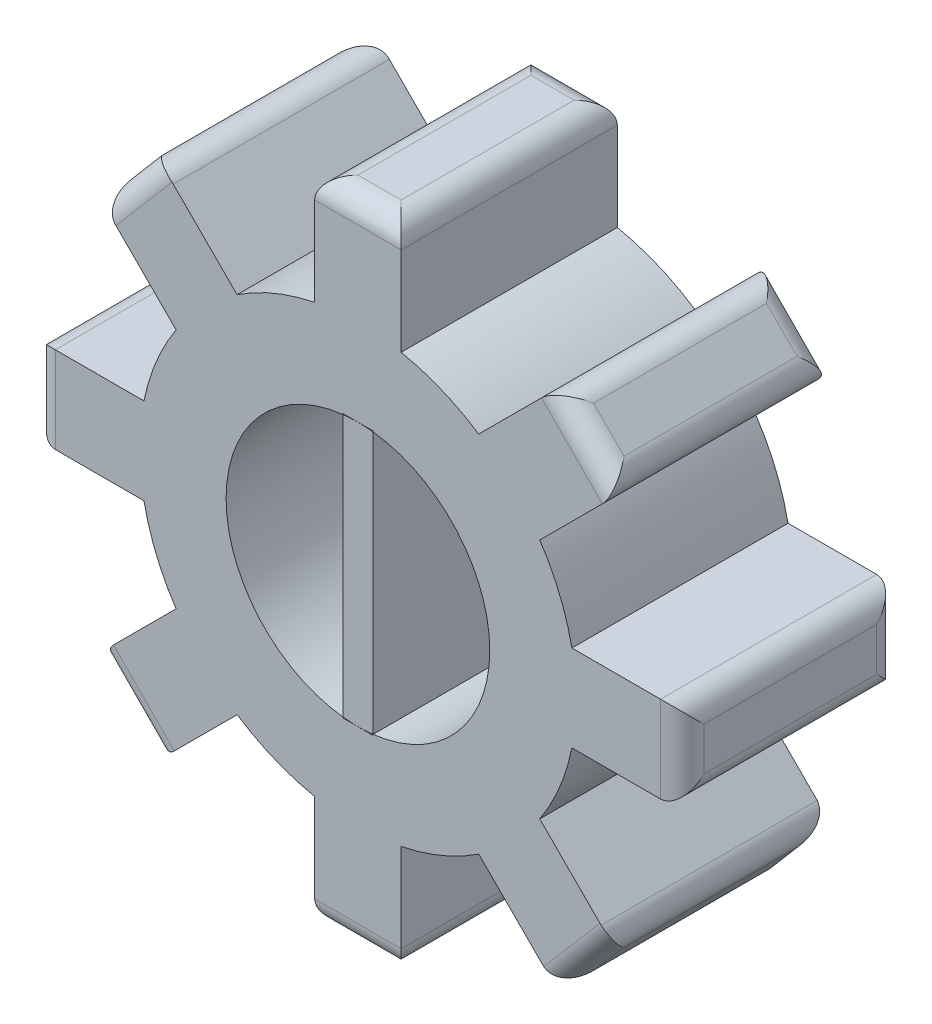
SolidWorks part; units mm, degrees
ref_plane "Front Plane" through (0, 0, 0) normal (0, 0, 1) x (1, 0, 0)
ref_plane "Top Plane" through (0, 0, 0) normal (0, 1, 0) x (1, 0, 0)
ref_plane "Right Plane" through (0, 0, 0) normal (1, 0, 0) x (0, 0, -1)
sketch "Sketch1" plane through (0, 0, 0) normal (0, 0, 1) x (1, 0, 0)
  line L1 (1, -7.5) -> (-1, -7.5)
  line L2 (1, -7.5) -> (1, 7.5)
  line L3 (1, 7.5) -> (-1, 7.5)
  line L4 (-1, -7.5) -> (-1, 7.5)
  line L5 (1, -7.5) -> (-1, 7.5) construction
  line L6 (1, 7.5) -> (-1, -7.5) construction
  line L7 (-7.5, -1) -> (7.5, -1)
  line L8 (-7.5, -1) -> (-7.5, 1)
  line L9 (-7.5, 1) -> (7.5, 1)
  line L10 (7.5, -1) -> (7.5, 1)
  line L11 (-7.5, -1) -> (7.5, 1) construction
  line L12 (-7.5, 1) -> (7.5, -1) construction
  line L13 (-6.007, -4.5928) -> (-4.5996, -6.0138)
  line L14 (-6.007, -4.5928) -> (4.5996, 6.0138)
  line L15 (4.5996, 6.0138) -> (6.007, 4.5928)
  line L16 (-4.5996, -6.0138) -> (6.007, 4.5928)
  line L17 (-6.007, -4.5928) -> (6.007, 4.5928) construction
  line L18 (4.5996, 6.0138) -> (-4.5996, -6.0138) construction
  line L22 (4.6549, -6.0646) -> (5.9517, -4.542)
  line L23 (4.6549, -6.0646) -> (-5.9517, 4.542)
  line L24 (-5.9517, 4.542) -> (-4.6549, 6.0646)
  line L25 (5.9517, -4.542) -> (-4.6549, 6.0646)
  line L26 (4.6549, -6.0646) -> (-4.6549, 6.0646) construction
  line L27 (-5.9517, 4.542) -> (5.9517, -4.542) construction
  line L29 (0.35, -3.05) -> (-0.35, -3.05)
  line L30 (0.35, -3.05) -> (0.35, 3.05)
  line L31 (0.35, 3.05) -> (-0.35, 3.05)
  line L32 (-0.35, -3.05) -> (-0.35, 3.05)
  line L33 (0.35, -3.05) -> (-0.35, 3.05) construction
  line L34 (0.35, 3.05) -> (-0.35, -3.05) construction
  circle A0 centre (0, 0) radius 3.05
  circle A1 centre (0, 0) radius 5.05
  point P20 (0, 0)
  dimension "D1" = 6.1
  dimension "D2" = 2
  dimension "D3" = 45
  dimension "D4" = 2
  dimension "D5" = 135
  dimension "D6" = 15
  dimension "D7" = 0.7
extrude "Boss-Extrude1" add sketch "Sketch1" along normal blind 5 contours A1 L2 L3 L4 | A1 L25 L24 L23 | A1 L16 L15 L14 | A1 L7 L10 L9 | A1 L23 L22 L25 | A1 L4 L1 L2 | A1 L14 L13 L16 | L16 A1 L14 A0 | L14 A1 L2 A0 | L2 A1 L4 A0 | L4 A1 L25 A0 | L25 A1 L23 A0 | L23 A1 L9 A0 | L9 A1 L7 A0 | L7 A1 L14 A0 | L14 A1 L16 A0 | L16 A1 L4 A0 | L2 A1 L23 A0 | L4 A1 L2 A0 | L25 A1 L7 A0 | L23 A1 L25 A0 | L7 A1 L9 A0 | L9 A1 L16 A0 | A1 L9 L8 L7 | L30 A0 L32 L25 L14 | L32 L14 L25 | L25 L30 L14 | L32 L9 L30 L25 L14 | L32 L7 L30 L9 | L32 A0 L30 L23 L16 | L32 L16 L23 | L23 L30 L16 | L32 L23 L16 L30 L7 region at (0, -6.2582, 0) region at (0, -4.0063, 0) region at (1.6319, -3.9354, 0) region at (-1.6307, -3.9367, 0) region at (4.4181, -4.4332, 0) region at (2.8323, -2.8323, 0) region at (-2.8321, -2.8321, 0) region at (-4.4248, -4.4257, 0) region at (0.0003, -2.3116, 0) region at (3.9354, -1.6319, 0) region at (-3.9367, -1.6307, 0) region at (0.2341, -1.4119, 0) region at (6.2582, 0, 0) region at (4.0052, 0, 0) region at (-0.2326, -1.4119, 0) region at (-4.0052, 0, 0) region at (-6.2582, 0, 0) region at (0.0017, -1.14, 0) region at (-3.9354, 1.6319, 0) region at (0, 0, 0) region at (3.9367, 1.6307, 0) region at (-2.8323, 2.8323, 0) region at (-4.4181, 4.4332, 0) region at (-0.0017, 1.14, 0) region at (4.4248, 4.4257, 0) region at (2.8321, 2.8321, 0) region at (-1.6319, 3.9354, 0) region at (0.2326, 1.4119, 0) region at (1.6307, 3.9367, 0) region at (-0.2341, 1.4119, 0) region at (0, 4.0063, 0) region at (0, 6.2582, 0) region at (-0.0003, 2.3116, 0)
fillet "Fillet1" radius 0.5 32 edges at (4.6549, -6.0646, 2.5) (5.3033, -5.3033, 5) (5.9517, -4.542, 2.5) (5.3033, -5.3033, 0) (7.5, -1, 2.5) (7.5, 0, 5) (7.5, 1, 2.5) (7.5, 0, 0) (6.007, 4.5928, 2.5) (5.3033, 5.3033, 5) (4.5996, 6.0138, 2.5) (5.3033, 5.3033, 0) (-4.6549, 6.0646, 2.5) (-5.3033, 5.3033, 5) (-5.9517, 4.542, 2.5) (-5.3033, 5.3033, 0) (-1, -7.5, 2.5) (0, -7.5, 5) (1, -7.5, 2.5) (0, -7.5, 0) (-6.007, -4.5928, 2.5) (-5.3033, -5.3033, 5) (-4.5996, -6.0138, 2.5) (-5.3033, -5.3033, 0) (-7.5, 1, 2.5) (-7.5, 0, 5) (-7.5, -1, 2.5) (-7.5, 0, 0) (1, 7.5, 2.5) (0, 7.5, 5) (-1, 7.5, 2.5) (0, 7.5, 0)
